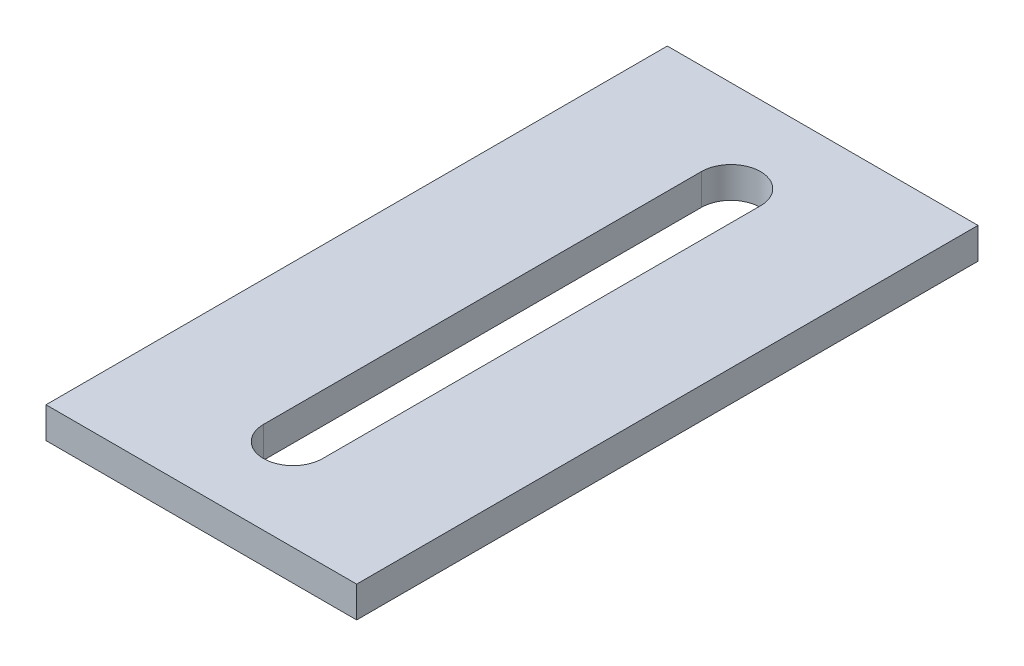
SolidWorks part; units mm, degrees
ref_plane "Front Plane" through (0, 0, 0) normal (0, 0, 1) x (1, 0, 0)
ref_plane "Top Plane" through (0, 0, 0) normal (0, 1, 0) x (1, 0, 0)
ref_plane "Right Plane" through (0, 0, 0) normal (1, 0, 0) x (0, 0, -1)
sketch "Sketch1" plane through (0, 0, 0) normal (0, 1, 0) x (1, 0, 0)
  line L0 (0, 35.2375) -> (0, -35.2375) construction
  line L1 (-25, 50) -> (25, 50)
  line L2 (-25, 50) -> (-25, -50)
  line L3 (-25, -50) -> (25, -50)
  line L4 (25, 50) -> (25, -50)
  line L5 (-25, 50) -> (25, -50) construction
  line L6 (-25, -50) -> (25, 50) construction
  line L7 (4.7625, 35.2375) -> (4.7625, -35.2375)
  line L8 (-4.7625, 35.2375) -> (-4.7625, -35.2375)
  arc A0 (4.7625, 35.2375) -> (-4.7625, 35.2375) centre (0, 35.2375) ccw
  arc A1 (-4.7625, -35.2375) -> (4.7625, -35.2375) centre (0, -35.2375) ccw
  point P0 (0, 0)
  point P8 (0, 0)
  point P13 (0, 40)
  point P14 (0, -40)
  dimension "D1" = 50
  dimension "D2" = 100
  dimension "D3" = 10
  dimension "D4" = 10
  dimension "D5" = 9.525
extrude "Boss-Extrude1" add sketch "Sketch1" along normal blind 2.5 and the other way blind 2.5
